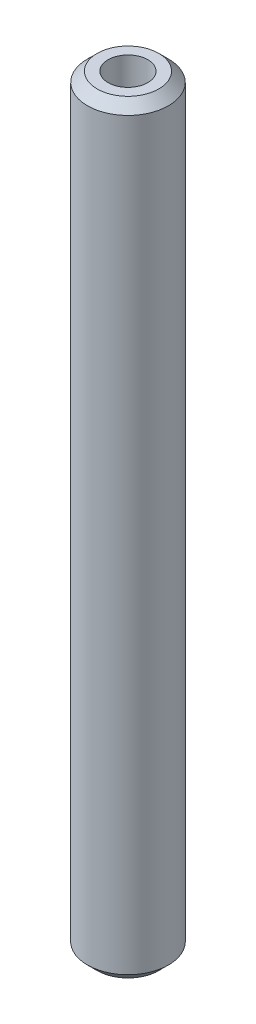
SolidWorks part; units mm, degrees
ref_plane "Front Plane" through (0, 0, 0) normal (0, 0, 1) x (1, 0, 0)
ref_plane "Top Plane" through (0, 0, 0) normal (0, 1, 0) x (1, 0, 0)
ref_plane "Right Plane" through (0, 0, 0) normal (1, 0, 0) x (0, 0, -1)
sketch "Sketch1" plane through (0, 0, 0) normal (0, 1, 0) x (1, 0, 0)
  circle A0 centre (0, 0) radius 5
  dimension "SHAFT_OD" = 10
extrude "Boss-Extrude1" add sketch "Sketch1" along normal blind 94.206
sketch "Sketch2" plane through (0, 0, 0) normal (0, 1, 0) x (1, 0, 0)
  circle A0 centre (0, 0) radius 2.4537
  dimension "BORE_D" = 4.9075
extrude "Cut-Extrude1" cut sketch "Sketch2" along normal through all
chamfer "Chamfer1" distance 1.1972 angle 45 2 edges at (0, 94.206, 5) (0, 0, 5)
